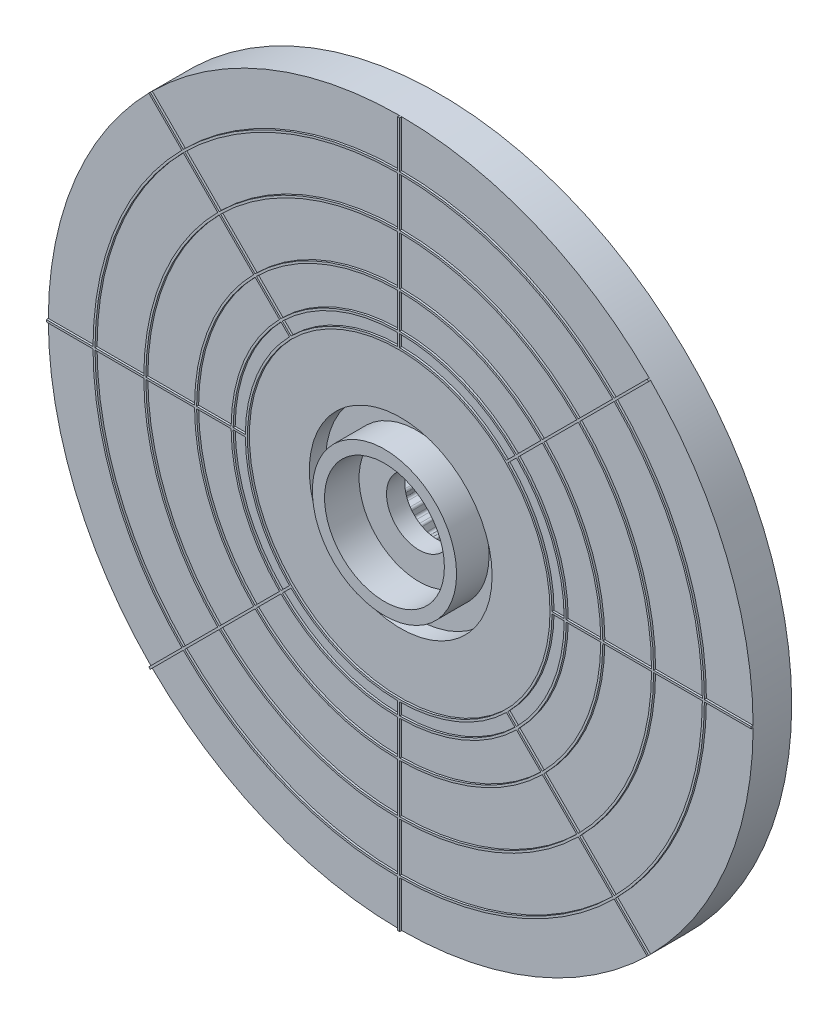
SolidWorks part; units mm, degrees
material "PVC hart"
ref_plane "Ebene vorne" through (0, 0, 0) normal (0, 0, 1) x (1, 0, 0)
ref_plane "Ebene oben" through (0, 0, 0) normal (0, 1, 0) x (1, 0, 0)
ref_plane "Ebene rechts" through (0, 0, 0) normal (1, 0, 0) x (0, 0, -1)
sketch "Skizze5" plane through (0, 0, 0) normal (1, 0, 0) x (0, 0, -1)
  line L0 (0, 0) -> (31.9699, 0) construction
  line L1 (0.75, 4.1) -> (3.1, 4.1)
  line L2 (3.1, 4.1) -> (3.1, 2.9)
  line L3 (3.1, 2.9) -> (0, 2.9)
  line L4 (0, 2.9) -> (0, 1.6)
  line L5 (0, 1.6) -> (-0.9, 1.6)
  line L6 (-0.9, 1.6) -> (-0.9, 2.95)
  line L7 (-0.9, 2.95) -> (-2.6, 2.95)
  line L8 (-2.6, 2.95) -> (-2.6, 3.55)
  line L9 (-2.6, 3.55) -> (-1, 3.55)
  line L10 (-1, 3.55) -> (-1, 4.5)
  line L11 (-1, 4.5) -> (-1.8, 4.5)
  line L12 (-1.8, 4.5) -> (-1.8, 20)
  line L13 (-1.8, 20) -> (0.1, 20)
  line L14 (0.1, 20) -> (0.1, 4.75)
  line L15 (0, 1.6) -> (0, 0) construction
  line L16 (0.1, 4.75) -> (0.75, 4.1)
  dimension "D1" = 8.2
  dimension "D2" = 5.8
  dimension "D3" = 135
  dimension "D4" = 3
  dimension "D5" = 1.9
  dimension "D6" = 9
  dimension "D7" = 7.1
  dimension "D8" = 5.9
  dimension "D9" = 3.2
  dimension "D10" = 3.1
  dimension "D11" = 5.7
  dimension "D12" = 1.7
  dimension "D13" = 40
  dimension "D14" = 0.8
  dimension "D15" = 9.5
revolve "Rotation2" add sketch "Skizze5" angle 360 about L0
ref_axis "Rotationsachse" through (0, 0, 0) along (0, 0, 1)
sketch "Skizze4" plane through (0, 0, -3.1) normal (0, 0, 1) x (1, 0, 0)
  line L0 (0, 0) -> (-0.3635, 2.8771) construction
  line L1 (-0.2786, 2.847) -> (-0.0723, 2.6309)
  line L2 (0.2786, 2.847) -> (0.0723, 2.6309)
  line L3 (0.3635, 2.8771) -> (0, 0) construction
  line L4 (0, 2.9) -> (0, 0) construction
  circle A0 centre (0, 0) radius 2.9 construction
  arc A2 (-0.3635, 2.8771) -> (0.3635, 2.8771) centre (0, 0) cw
  circle A3 centre (0, 0) radius 2.6 construction
  arc A4 (-0.0723, 2.6309) -> (0.0723, 2.6309) centre (0, 2.7) ccw
  arc A5 (-0.3635, 2.8771) -> (-0.2786, 2.847) centre (-0.3509, 2.7779) cw
  arc A6 (0.3635, 2.8771) -> (0.2786, 2.847) centre (0.3509, 2.7779) ccw
  point P14 (0, 2.6)
  dimension "D2" = 5.2
  dimension "D3" = 0.1
  dimension "D1" = 14.4
extrude "Aufsatz-Linear austragen4" add sketch "Skizze4" along normal up to surface (3.1 mm away) up to face at (2.9, 0, 0)
pattern_circular "Kreismuster1" count 25 over 360 about axis through (0, 0, 0) along (0, 0, 1) of "Aufsatz-Linear austragen4"
sketch "Skizze6" plane through (0, 0, 1.8) normal (0, 0, 1) x (1, 0, 0)
  circle A0 centre (0, 0) radius 17.35
  dimension "D1" = 34.7
extrude "Rund1" cut sketch "Skizze6" against normal through all flip side to cut
sketch "Skizze7" plane through (0, 0, 1.8) normal (0, 0, 1) x (1, 0, 0)
  line L0 (0, 17.35) -> (0, 7.5)
  line L1 (7.5, 0) -> (17.35, 0)
  line L2 (0, -7.5) -> (0, -17.35)
  line L3 (-7.5, 0) -> (-17.35, 0)
  line L4 (5.3033, 5.3033) -> (12.2683, 12.2683)
  line L5 (5.3033, -5.3033) -> (12.2683, -12.2683)
  line L6 (-5.3033, -5.3033) -> (-12.2683, -12.2683)
  line L7 (-5.3033, 5.3033) -> (-12.2683, 12.2683)
  line L8 (-17.35, 0) -> (-12.2683, 12.2683) construction
  line L9 (0, 17.35) -> (-12.2683, 12.2683) construction
  line L10 (0, 17.35) -> (12.2683, 12.2683) construction
  line L11 (12.2683, 12.2683) -> (17.35, 0) construction
  line L12 (17.35, 0) -> (12.2683, -12.2683) construction
  line L13 (12.2683, -12.2683) -> (0, -17.35) construction
  line L14 (0, -17.35) -> (-12.2683, -12.2683) construction
  line L15 (-12.2683, -12.2683) -> (-17.35, 0) construction
  circle A0 centre (0, 0) radius 10
  circle A1 centre (0, 0) radius 12.5
  circle A2 centre (0, 0) radius 15
  circle A3 centre (0, 0) radius 7.5
  circle A4 centre (0, 0) radius 8.2
  circle A5 centre (0, 0) radius 17.35 construction
  dimension "D1" = 15
  dimension "D2" = 16.4
  dimension "D3" = 20
  dimension "D4" = 25
  dimension "D5" = 30
extrude "Rund2" add sketch "Skizze7" along normal blind 0.1 thin contours A3 | A4 | A0 | A1 | A2 | L0 | L7 | L3 | L6 | L2 | L5 | L1 | L4 thin type mid plane wall 0.1
sketch "Skizze9" [suppressed] plane through (0, 0, 1.8) normal (0, 0, 1) x (1, 0, 0)
  line L0 (-4.275, 7.1726) -> (-2.3589, 17.3923)
  line L1 (2.3589, 17.3923) -> (4.275, 7.1726)
  line L2 (0, 16.95) -> (0, -16.95) construction
  line L3 (-4.275, -7.1726) -> (-2.3589, -17.3923)
  line L4 (7.65, 0) -> (10.7, 0) construction
  line L5 (10.7, 0) -> (13.75, 0) construction
  line L6 (13.75, 0) -> (16.95, 0)
  line L7 (16.95, 0) -> (20, 0) construction
  line L8 (2.3589, -17.3923) -> (4.275, -7.1726)
  arc A0 (-2.3589, 17.3923) -> (2.3589, 17.3923) centre (0, 16.95) cw
  circle A1 centre (0, 0) radius 20 construction
  circle A2 centre (0, -7.65) radius 0.9
  circle A3 centre (0, 0) radius 16.95 construction
  circle A4 centre (0, 0) radius 8.35 construction
  circle A6 centre (0, 0) radius 6.75 construction
  circle A7 centre (0, 16.95) radius 0.9
  circle A8 centre (0, 13.75) radius 0.9
  circle A9 centre (0, 10.7) radius 0.9
  circle A10 centre (0, 7.65) radius 0.9
  circle A11 centre (0, 0) radius 13.75 construction
  circle A12 centre (0, 0) radius 10.7 construction
  circle A13 centre (0, 0) radius 7.65 construction
  circle A14 centre (0, -10.7) radius 0.9
  circle A15 centre (0, -13.75) radius 0.9
  circle A16 centre (0, -16.95) radius 0.9
  arc A17 (-2.3589, -17.3923) -> (2.3589, -17.3923) centre (0, -16.95) ccw
  arc A18 (-4.275, 7.1726) -> (-4.275, -7.1726) centre (33.9807, 0) ccw
  arc A19 (4.275, -7.1726) -> (4.275, 7.1726) centre (-33.9807, 0) ccw
  dimension "D1" = 2.4
  dimension "D3" = 15.3
  dimension "D4" = 16.7
  dimension "D6" = 13.5
  dimension "D8" = 1.8
  dimension "D2" = 8.55
  dimension "D7" = 3.2
extrude "2er" [suppressed] cut sketch "Skizze9" against normal through all and the other way through all flip side to cut
sketch "Skizze8" [suppressed] plane through (0, 0, 1.8) normal (0, 0, 1) x (1, 0, 0)
  line L0 (-4.275, 7.1726) -> (-2.3589, 17.3923)
  line L1 (2.3589, 17.3923) -> (4.275, 7.1726)
  line L2 (0, 16.95) -> (0, -16.95) construction
  line L3 (0, 0) -> (14.1421, 14.1421) construction
  line L4 (7.65, 0) -> (10.7, 0) construction
  line L5 (10.7, 0) -> (13.75, 0) construction
  line L6 (13.75, 0) -> (16.95, 0)
  line L7 (16.95, 0) -> (20, 0) construction
  line L8 (7.1726, 4.275) -> (17.3923, 2.3589)
  line L9 (17.3923, -2.3589) -> (7.1726, -4.275)
  line L10 (4.275, -7.1726) -> (2.3589, -17.3923)
  line L11 (-2.3589, -17.3923) -> (-4.275, -7.1726)
  line L12 (-7.1726, -4.275) -> (-17.3923, -2.3589)
  line L13 (-17.3923, 2.3589) -> (-7.1726, 4.275)
  arc A0 (-2.3589, 17.3923) -> (2.3589, 17.3923) centre (0, 16.95) cw
  arc A1 (4.275, 7.1726) -> (7.1726, 4.275) centre (6.3522, 6.3522) ccw
  circle A2 centre (0, 0) radius 8.9834 construction
  circle A3 centre (0, 0) radius 16.95 construction
  circle A4 centre (0, 0) radius 8.35 construction
  circle A5 centre (0, 0) radius 20 construction
  circle A6 centre (0, 0) radius 6.75 construction
  circle A7 centre (0, 16.95) radius 0.9
  circle A8 centre (0, 13.75) radius 0.9
  circle A9 centre (0, 10.7) radius 0.9
  circle A10 centre (0, 7.65) radius 0.9
  circle A11 centre (0, 0) radius 13.75 construction
  circle A12 centre (0, 0) radius 10.7 construction
  circle A13 centre (0, 0) radius 7.65 construction
  arc A14 (17.3923, 2.3589) -> (17.3923, -2.3589) centre (16.95, 0) cw
  circle A15 centre (16.95, 0) radius 0.9
  circle A16 centre (13.75, 0) radius 0.9
  circle A17 centre (10.7, 0) radius 0.9
  circle A18 centre (7.65, 0) radius 0.9
  arc A19 (7.1726, -4.275) -> (4.275, -7.1726) centre (6.3522, -6.3522) ccw
  arc A20 (2.3589, -17.3923) -> (-2.3589, -17.3923) centre (0, -16.95) cw
  circle A21 centre (0, -16.95) radius 0.9
  circle A22 centre (0, -13.75) radius 0.9
  circle A23 centre (0, -10.7) radius 0.9
  circle A24 centre (0, -7.65) radius 0.9
  arc A25 (-4.275, -7.1726) -> (-7.1726, -4.275) centre (-6.3522, -6.3522) ccw
  arc A26 (-17.3923, -2.3589) -> (-17.3923, 2.3589) centre (-16.95, 0) cw
  circle A27 centre (-16.95, 0) radius 0.9
  circle A28 centre (-13.75, 0) radius 0.9
  circle A29 centre (-10.7, 0) radius 0.9
  circle A30 centre (-7.65, 0) radius 0.9
  arc A31 (-7.1726, 4.275) -> (-4.275, 7.1726) centre (-6.3522, 6.3522) ccw
  point P77 (0, 0)
  circle M1 centre (0, 0) radius 4.5
  dimension "D1" = 2.4
  dimension "D3" = 15.3
  dimension "D4" = 16.7
  dimension "D6" = 13.5
  dimension "D8" = 1.8
  dimension "D2" = 8.55
  dimension "D5" = 45
  dimension "D7" = 3.2
  dimension "D9" = 4
extrude "4er" [suppressed] cut sketch "Skizze8" against normal through all and the other way through all flip side to cut contours A31 L13 A26 L12 A25 L11 A20 L10 A19 L9 A14 L8 A1 L1 A0 L0 A30 A29 A28 A27 A24 A23 A22 A21 A18 A17 A16 A15 A10 A9 A8 A7 M1 | M1
sketch "Skizze10" [suppressed] plane through (0, 0, 1.8) normal (0, 0, 1) x (1, 0, 0)
  line L0 (7.6, 0) -> (9.9, 0) construction
  line L1 (9.9, 0) -> (12.75, 0) construction
  line L2 (0, 12.75) -> (0, -12.75) construction
  line L3 (-3.4, 5.889) -> (-2.3761, 13.088)
  line L4 (2.3761, 13.088) -> (3.4, 5.889)
  line L5 (-3.4, 5.889) -> (0, 0) construction
  line L6 (0, 0) -> (3.4, 5.889) construction
  line L7 (-3.4, 5.889) -> (3.4, 5.889) construction
  line L8 (3.4, 5.889) -> (10.1465, 8.6017)
  line L9 (12.5225, 4.4862) -> (6.8, 0)
  line L10 (6.8, 0) -> (12.5225, -4.4862)
  line L11 (10.1465, -8.6017) -> (3.4, -5.889)
  line L12 (3.4, -5.889) -> (2.3761, -13.088)
  line L13 (-2.3761, -13.088) -> (-3.4, -5.889)
  line L14 (-3.4, -5.889) -> (-10.1465, -8.6017)
  line L15 (-12.5225, -4.4862) -> (-6.8, 0)
  line L16 (-6.8, 0) -> (-12.5225, 4.4862)
  line L17 (-10.1465, 8.6017) -> (-3.4, 5.889)
  circle A0 centre (0, 0) radius 7.6 construction
  circle A1 centre (0, 0) radius 9.9 construction
  circle A2 centre (0, 0) radius 12.75 construction
  circle A3 centre (0, 7.6) radius 0.9
  circle A4 centre (0, 9.9) radius 0.9
  circle A5 centre (0, 12.75) radius 0.9
  arc A6 (-2.3761, 13.088) -> (2.3761, 13.088) centre (0, 12.75) cw
  circle A7 centre (0, 0) radius 6.8 construction
  circle A8 centre (6.5818, 3.8) radius 0.9
  circle A9 centre (8.5737, 4.95) radius 0.9
  circle A10 centre (11.0418, 6.375) radius 0.9
  arc A11 (10.1465, 8.6017) -> (12.5225, 4.4862) centre (11.0418, 6.375) cw
  circle A12 centre (6.5818, -3.8) radius 0.9
  circle A13 centre (8.5737, -4.95) radius 0.9
  circle A14 centre (11.0418, -6.375) radius 0.9
  arc A15 (12.5225, -4.4862) -> (10.1465, -8.6017) centre (11.0418, -6.375) cw
  circle A16 centre (0, -7.6) radius 0.9
  circle A17 centre (0, -9.9) radius 0.9
  circle A18 centre (0, -12.75) radius 0.9
  arc A19 (2.3761, -13.088) -> (-2.3761, -13.088) centre (0, -12.75) cw
  circle A20 centre (-6.5818, -3.8) radius 0.9
  circle A21 centre (-8.5737, -4.95) radius 0.9
  circle A22 centre (-11.0418, -6.375) radius 0.9
  arc A23 (-10.1465, -8.6017) -> (-12.5225, -4.4862) centre (-11.0418, -6.375) cw
  circle A24 centre (-6.5818, 3.8) radius 0.9
  circle A25 centre (-8.5737, 4.95) radius 0.9
  circle A26 centre (-11.0418, 6.375) radius 0.9
  arc A27 (-12.5225, 4.4862) -> (-10.1465, 8.6017) centre (-11.0418, 6.375) cw
  point P72 (0, 0)
  dimension "D1" = 1.8
  dimension "D3" = 15.2
  dimension "D4" = 2.4
  dimension "D5" = 19.8
  dimension "D6" = 25.5
  dimension "D7" = 6
  dimension "D2" = 6.8
extrude "Schnitt-Linear austragen2" [suppressed] cut sketch "Skizze10" against normal through all flip side to cut
